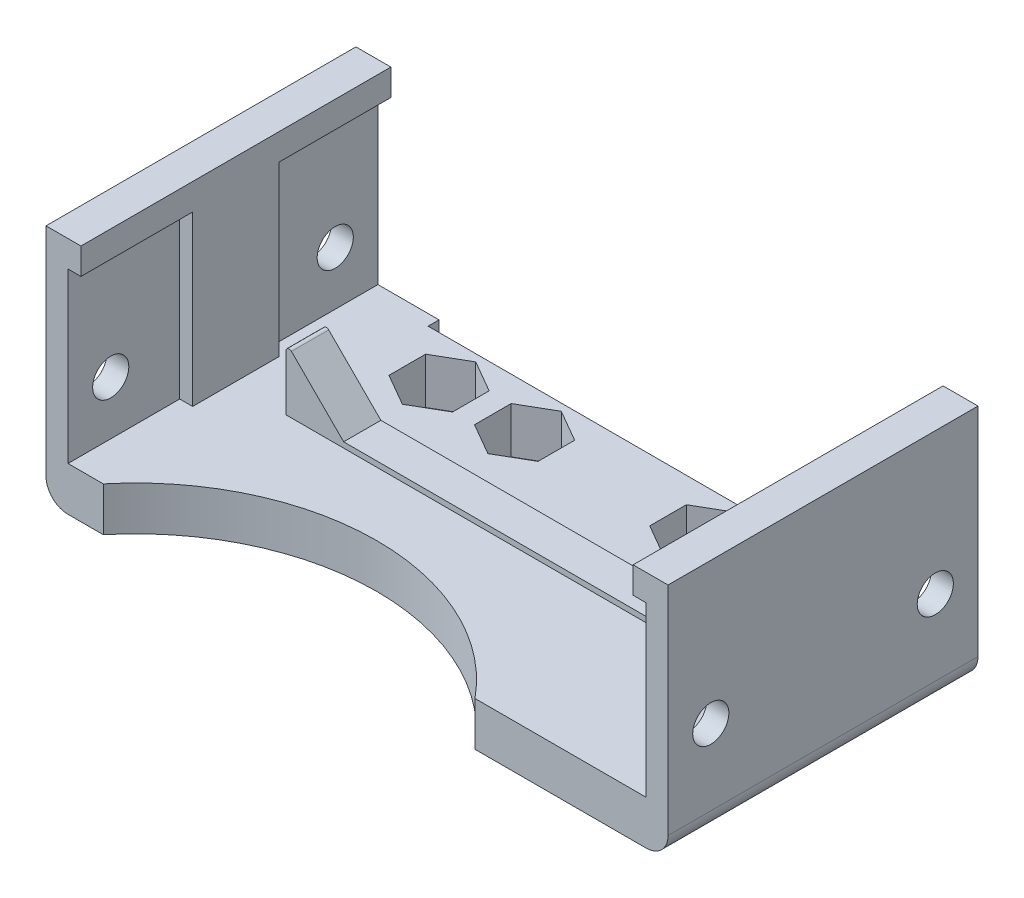
SolidWorks part; units mm, degrees
ref_plane "Front Plane" through (0, 0, 0) normal (0, 0, 1) x (1, 0, 0)
ref_plane "Top Plane" through (0, 0, 0) normal (0, 1, 0) x (1, 0, 0)
ref_plane "Right Plane" through (0, 0, 0) normal (1, 0, 0) x (0, 0, -1)
sketch "Sketch1" plane through (0, 0, 0) normal (0, 0, 1) x (1, 0, 0)
  line L0 (0, 21.81) -> (3.19, 21.81)
  line L1 (0, 21.81) -> (0, 2)
  line L2 (2, 0) -> (54.8, 0)
  line L3 (56.8, 21.81) -> (56.8, 2)
  line L18 (53.61, 21.81) -> (56.8, 21.81)
  line L54 (53.61, 4.02) -> (53.61, 21.81)
  line L55 (3.19, 21.81) -> (3.19, 4.02)
  line L57 (3.19, 4.02) -> (53.61, 4.02)
  arc A0 (54.8, 0) -> (56.8, 2) centre (54.8, 2) ccw
  arc A1 (0, 2) -> (2, 0) centre (2, 2) ccw
extrude "Boss-Extrude1" add sketch "Sketch1" along normal blind 28.3
sketch "Sketch2" plane through (0, 0, 0) normal (0, 0, 1) x (1, 0, 0)
  line L0 (2.01, 19.4) -> (54.79, 19.4)
  line L1 (2.01, 19.4) -> (2.01, 4.02)
  line L2 (2.01, 4.02) -> (54.79, 4.02)
  line L3 (54.79, 19.4) -> (54.79, 4.02)
extrude "Cut-Extrude1" cut sketch "Sketch2" along normal blind 10.2
extrude "Cut-Extrude2" cut sketch "Sketch2<2>" against normal blind 10.2 from surface starting at face at (28.4, 9.8452, 28.3)
sketch "Sketch2<2>" plane through (0, 0, 0) normal (0, 0, 1) x (1, 0, 0) same geometry as "Sketch2"
sketch "Sketch3" plane through (0, 0, 0) normal (-1, 0, 0) x (0, 0, 1)
  circle A0 centre (3.9, 8.91) radius 1.65
  circle A1 centre (24.4, 8.91) radius 1.65
extrude "Cut-Extrude3" cut sketch "Sketch3" against normal up to surface (56.8 mm away) up to face at (56.8, 11.905, 14.15)
sketch "Sketch4" plane through (0, 0, 0) normal (0, 0, 1) x (1, 0, 0)
  line L0 (8.6121, 9.286) -> (13.3782, 4.52)
  line L3 (8.1, 4.02) -> (48.7, 4.02)
  line L5 (13.3782, 4.52) -> (43.4218, 4.52)
  line L6 (43.4218, 4.52) -> (48.1879, 9.286)
  line L12 (8.1, 4.02) -> (8.1, 9.0739)
  line L13 (48.7, 4.02) -> (48.7, 9.0739)
  arc A0 (48.7, 9.0739) -> (48.1879, 9.286) centre (48.4, 9.0739) ccw
  arc A1 (8.1, 9.0739) -> (8.6121, 9.286) centre (8.4, 9.0739) cw
extrude "Boss-Extrude2" add sketch "Sketch4" along normal blind 3.4 from offset 11.1
sketch "Sketch5" plane through (0, 0, 0) normal (0, -1, 0) x (1, 0, 0)
  line L0 (5.2294, 28.3) -> (39.1706, 28.3)
  arc A1 (5.2294, 28.3) -> (39.1706, 28.3) centre (22.2, 42.3) ccw
extrude "Cut-Extrude4" cut sketch "Sketch5" against normal up to surface (4.02 mm away) up to face at (28.4, 4.02, 12.8)
sketch "Sketch6" plane through (0, 0, 0) normal (0, -1, 0) x (1, 0, 0)
  line L46 (9.09, 1) -> (23.9, 1)
  line L52 (32.9, 9) -> (47.71, 9)
  line L54 (32.9, 1) -> (47.71, 1)
  line L55 (9.09, 9) -> (23.9, 9)
  line L64 (7.59, 7.5) -> (7.59, 2.5)
  line L66 (25.4, 7.5) -> (25.4, 2.5)
  line L69 (31.4, 7.5) -> (31.4, 2.5)
  line L71 (49.21, 7.5) -> (49.21, 2.5)
  circle A6 centre (20.4, 5) radius 1.65
  circle A7 centre (36.4, 5) radius 1.65
  circle A22 centre (12.59, 5) radius 1.65
  circle A23 centre (44.21, 5) radius 1.65
  arc A39 (32.9, 9) -> (31.4, 7.5) centre (32.9, 7.5) ccw
  arc A42 (47.71, 9) -> (49.21, 7.5) centre (47.71, 7.5) cw
  arc A49 (9.09, 9) -> (7.59, 7.5) centre (9.09, 7.5) ccw
  arc A52 (23.9, 9) -> (25.4, 7.5) centre (23.9, 7.5) cw
  arc A57 (23.9, 1) -> (25.4, 2.5) centre (23.9, 2.5) ccw
  arc A58 (9.09, 1) -> (7.59, 2.5) centre (9.09, 2.5) cw
  arc A59 (47.71, 1) -> (49.21, 2.5) centre (47.71, 2.5) ccw
  arc A60 (32.9, 1) -> (31.4, 2.5) centre (32.9, 2.5) cw
extrude "Boss-Extrude3" add sketch "Sketch6" along normal blind 3.2
sketch "Sketch8" plane through (0, 4.02, 0) normal (0, -1, 0) x (1, 0, 0)
  line L0 (23.3, 6.6743) -> (20.4, 8.3486)
  line L7 (20.4, 8.3486) -> (17.5, 6.6743)
  line L8 (17.5, 6.6743) -> (17.5, 3.3257)
  line L21 (17.5, 3.3257) -> (20.4, 1.6514)
  line L22 (20.4, 1.6514) -> (23.3, 3.3257)
  line L23 (23.3, 3.3257) -> (23.3, 6.6743)
  line L25 (39.3, 6.6743) -> (36.4, 8.3486)
  line L26 (36.4, 8.3486) -> (33.5, 6.6743)
  line L27 (33.5, 6.6743) -> (33.5, 3.3257)
  line L28 (33.5, 3.3257) -> (36.4, 1.6514)
  line L29 (36.4, 1.6514) -> (39.3, 3.3257)
  line L30 (39.3, 3.3257) -> (39.3, 6.6743)
  line L33 (47.11, 6.6743) -> (44.21, 8.3486)
  line L34 (44.21, 8.3486) -> (41.31, 6.6743)
  line L35 (41.31, 6.6743) -> (41.31, 3.3257)
  line L36 (41.31, 3.3257) -> (44.21, 1.6514)
  line L37 (44.21, 1.6514) -> (47.11, 3.3257)
  line L38 (47.11, 3.3257) -> (47.11, 6.6743)
  line L40 (15.49, 6.6743) -> (12.59, 8.3486)
  line L41 (12.59, 8.3486) -> (9.69, 6.6743)
  line L42 (9.69, 6.6743) -> (9.69, 3.3257)
  line L43 (9.69, 3.3257) -> (12.59, 1.6514)
  line L44 (12.59, 1.6514) -> (15.49, 3.3257)
  line L45 (15.49, 3.3257) -> (15.49, 6.6743)
extrude "Cut-Extrude5" cut sketch "Sketch8" along normal offset from surface (4.22 mm away) 3 up to face at (20.4, -3.2, 3.35)
sketch "Sketch10" plane through (0, 0, 0) normal (0, 0, -1) x (-1, 0, 0)
  line L1 (-7.59, -4.4) -> (-49.21, -4.4)
  line L2 (-7.59, -4.4) -> (-7.59, 4.02)
  line L3 (-7.59, 4.02) -> (-49.21, 4.02)
  line L4 (-49.21, -4.4) -> (-49.21, 4.02)
extrude "Cut-Extrude6" cut sketch "Sketch10" against normal blind 1
